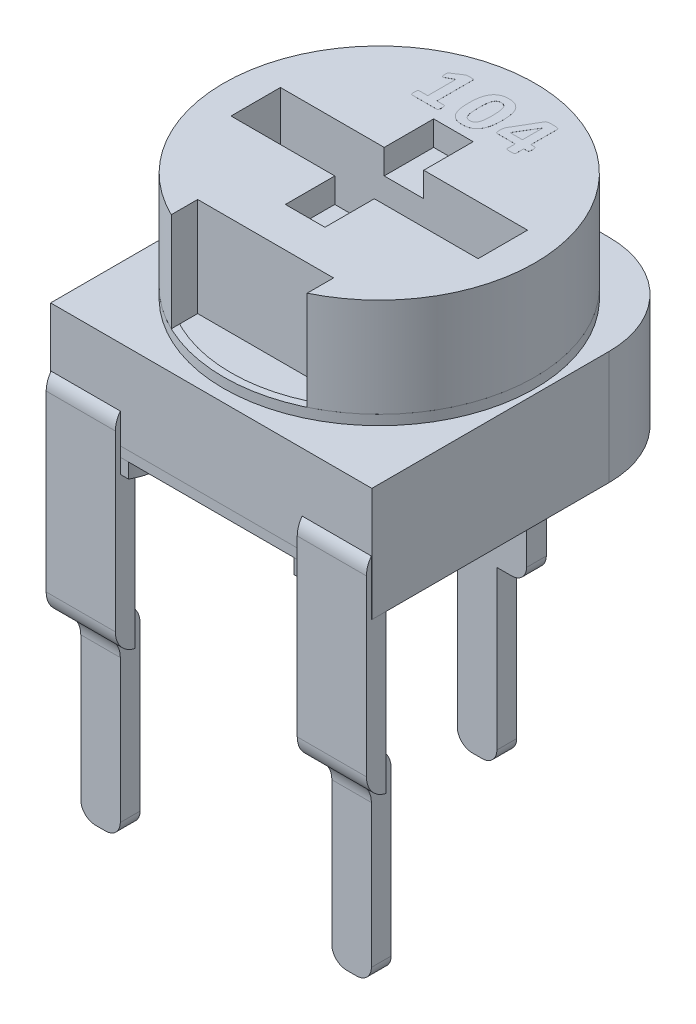
SolidWorks part; units mm, degrees
material "ABS"
ref_plane "Front Plane" through (0, 0, 0) normal (0, 0, 1) x (1, 0, 0)
ref_plane "Top Plane" through (0, 0, 0) normal (0, 1, 0) x (1, 0, 0)
ref_plane "Right Plane" through (0, 0, 0) normal (1, 0, 0) x (0, 0, -1)
sketch "Sketch1" plane through (0, 0, 0) normal (0, 1, 0) x (1, 0, 0)
  line L0 (0, 3.15) -> (0, -3.15) construction
  line L1 (0, 3.15) -> (0, 3.4) construction
  line L2 (0, -3.15) -> (0, -3.4) construction
  line L3 (-3.15, 0) -> (3.15, 0) construction
  line L4 (3.15, 0) -> (3.25, 0) construction
  line L5 (-3.15, 0) -> (-3.25, 0) construction
  line L6 (-3.25, -3.4) -> (3.25, -3.4)
  line L7 (-3.25, -3.4) -> (-3.25, 3.4)
  line L8 (-3.25, 3.4) -> (3.25, 3.4)
  line L9 (3.25, 3.4) -> (3.25, -3.4)
  circle A0 centre (0, 0) radius 3.15 construction
  dimension "D1" = 6.3
  dimension "D2" = 6.8
  dimension "D3" = 6.5
extrude "Boss-Extrude1" add sketch "Sketch1" along normal blind 2.3
sketch "Sketch2" plane through (0, 2.3, 0) normal (0, 1, 0) x (1, 0, 0)
  circle A0 centre (0, 0) radius 3.15 construction
  circle A1 centre (0, 0) radius 3.15
extrude "Boss-Extrude2" add sketch "Sketch2" along normal blind 0.2
fillet "Fillet1" radius 2 2 edges at (3.25, 1.15, -3.4) (-3.25, 1.15, -3.4)
sketch "Sketch3" plane through (0, 0, 0) normal (0, -1, 0) x (1, 0, 0)
  line L0 (0, 0) -> (0, -2.5) construction
  line L1 (-1.75, -2.5) -> (1.75, -2.5)
  line L6 (-2.25, -2) -> (-2.25, 2)
  line L7 (2.25, -2) -> (2.25, 2)
  line L8 (-2.25, 2) -> (-3, 2)
  line L9 (-3, 2) -> (-3, 3.4)
  line L10 (-3.25, 3.4) -> (3.25, 3.4) construction
  line L11 (2.25, 2) -> (3, 2)
  line L12 (3, 2) -> (3, 3.4)
  line L13 (3, 3.4) -> (-3, 3.4)
  line L14 (0, 0) -> (0, 3.4) construction
  arc A0 (-1.75, -2.5) -> (-2.25, -2) centre (-1.75, -2) cw
  arc A1 (1.75, -2.5) -> (2.25, -2) centre (1.75, -2) ccw
  point P20 (2.25, -2.5)
  dimension "D6" = 0.5
  dimension "D1" = 4.5
  dimension "D2" = 2.5
  dimension "D3" = 4.5
  dimension "D4" = 1.4
  dimension "D5" = 6
extrude "Cut-Extrude1" cut sketch "Sketch3" against normal blind 0.5
sketch "Sketch4" plane through (0, 0.5, 0) normal (0, -1, 0) x (1, 0, 0)
  line L8 (-3, 2) -> (-2.25, 2)
  line L9 (-2.25, 2) -> (-2.25, -2)
  line L10 (-1.75, -2.5) -> (1.75, -2.5)
  line L11 (2.25, -2) -> (2.25, 2)
  line L12 (2.25, 2) -> (3, 2)
  line L13 (3, 2) -> (3, 3.4)
  line L14 (3, 3.4) -> (-3, 3.4)
  line L15 (-3, 3.4) -> (-3, 2)
  line L16 (-3, 2) -> (-2.25, 2)
  line L17 (-2.25, 2) -> (-2.25, -2)
  line L18 (-1.75, -2.5) -> (1.75, -2.5)
  line L19 (2.25, -2) -> (2.25, 2)
  line L20 (2.25, 2) -> (3, 2)
  line L21 (3, 2) -> (3, 3.4)
  line L22 (3, 3.4) -> (-3, 3.4)
  line L23 (-3, 3.4) -> (-3, 2)
  arc A2 (-2.25, -2) -> (-1.75, -2.5) centre (-1.75, -2) ccw
  arc A3 (1.75, -2.5) -> (2.25, -2) centre (1.75, -2) ccw
  arc A4 (-2.25, -2) -> (-1.75, -2.5) centre (-1.75, -2) ccw
  arc A5 (1.75, -2.5) -> (2.25, -2) centre (1.75, -2) ccw
  dimension "D1" = 0
extrude "Boss-Extrude3" add sketch "Sketch4" along normal blind 0.2 separate body
sketch "Sketch5" plane through (0, 0.3, 0) normal (0, -1, 0) x (1, 0, 0)
  line L0 (0, 3.4) -> (0, 2.9) construction
  line L1 (3, 3.4) -> (-3, 3.4) construction
  line L2 (0, 2.9) -> (0, -2.18) construction
  line L3 (-2.54, 2.9) -> (2.54, 2.9) construction
  circle A0 centre (2.54, 2.9) radius 1
  circle A1 centre (-2.54, 2.9) radius 1
  circle A2 centre (0, -2.18) radius 1
  dimension "D2" = 5.08
  dimension "D4" = 2
  dimension "D1" = 0.5
  dimension "D3" = 5.08
extrude "Boss-Extrude4" add sketch "Sketch5" along normal up to surface (0.3 mm away) up to face at (0, 0, 0.1228)
sketch "Sketch6" plane through (0, 0.3, 0) normal (0, 1, 0) x (1, 0, 0)
  line L0 (-3.25, -3.4) -> (-3.25, -1)
  line L1 (-3.25, 1.4) -> (-3.25, -3.4) construction
  line L2 (-3.25, -1) -> (-4.35, -1)
  line L3 (-4.35, -1) -> (-4.35, -4.5)
  line L4 (-4.35, -4.5) -> (4.35, -4.5)
  line L5 (4.35, -4.5) -> (4.35, -1)
  line L6 (4.35, -1) -> (3.25, -1)
  line L7 (3.25, -3.4) -> (3.25, 1.4) construction
  line L8 (-3.25, -3.4) -> (3.25, -3.4)
  line L9 (3.25, -3.4) -> (3.25, -1)
  line L10 (0, 0) -> (0, -3.4) construction
  line L11 (0, -3.4) -> (0, -4.5) construction
  dimension "D1" = 3.5
extrude "Cut-Extrude2" cut sketch "Sketch6" against normal up to surface (0.3 mm away) up to face at (0, 0, -0.817)
sketch "Sketch8" plane through (0, 0.3, 0) normal (0, -1, 0) x (1, 0, 0)
  line L1 (-0.4, -1.98) -> (0.4, -1.98)
  line L2 (-0.4, -1.98) -> (-0.4, -2.38)
  line L3 (-0.4, -2.38) -> (0.4, -2.38)
  line L4 (0.4, -1.98) -> (0.4, -2.38)
  line L5 (-0.4, -1.98) -> (0.4, -2.38) construction
  line L6 (-0.4, -2.38) -> (0.4, -1.98) construction
  line L7 (-2.94, 3.1) -> (-2.14, 3.1)
  line L8 (-2.94, 3.1) -> (-2.94, 2.7)
  line L9 (-2.94, 2.7) -> (-2.14, 2.7)
  line L10 (-2.14, 3.1) -> (-2.14, 2.7)
  line L11 (-2.94, 3.1) -> (-2.14, 2.7) construction
  line L12 (-2.94, 2.7) -> (-2.14, 3.1) construction
  line L13 (2.94, 3.1) -> (2.14, 3.1)
  line L14 (2.94, 3.1) -> (2.94, 2.7)
  line L15 (2.94, 2.7) -> (2.14, 2.7)
  line L16 (2.14, 3.1) -> (2.14, 2.7)
  line L17 (2.94, 3.1) -> (2.14, 2.7) construction
  line L18 (2.94, 2.7) -> (2.14, 3.1) construction
  point P0 (0, -2.18)
  point P5 (-2.54, 2.9)
  point P11 (2.54, 2.9)
  dimension "D1" = 0.4
  dimension "D2" = 0.8
extrude "Boss-Extrude5" add sketch "Sketch8" along normal blind 7
sketch "Sketch9" plane through (0, 0.3, 0) normal (0, -1, 0) x (1, 0, 0)
  line L4 (0, -1.98) -> (0, -2.38) construction
  line L5 (0.4, -1.98) -> (-0.4, -1.98) construction
  line L6 (-0.4, -2.38) -> (0.4, -2.38) construction
  line L8 (-1, -1.98) -> (1, -1.98)
  line L9 (-1, -1.98) -> (-1, -2.38)
  line L10 (-1, -2.38) -> (1, -2.38)
  line L11 (1, -1.98) -> (1, -2.38)
  line L12 (-1, -1.98) -> (1, -2.38) construction
  line L13 (-1, -2.38) -> (1, -1.98) construction
  point P14 (0, -2.18)
  dimension "D1" = 2
extrude "Boss-Extrude6" add sketch "Sketch9" along normal blind 3.5
sketch "Sketch10" plane through (0, 0.3, 0) normal (0, -1, 0) x (1, 0, 0)
  line L0 (-2.54, 3.1) -> (-2.54, 3.5) construction
  line L1 (-2.14, 3.1) -> (-2.94, 3.1) construction
  line L2 (2.54, 3.1) -> (2.54, 3.5) construction
  line L3 (2.94, 3.1) -> (2.14, 3.1) construction
  line L4 (-2.94, 3.1) -> (-2.94, 2.7) construction
  line L5 (-3.24, 3.5) -> (-1.84, 3.5)
  line L6 (-3.24, 3.5) -> (-3.24, 3.1)
  line L7 (-3.24, 3.1) -> (-1.84, 3.1)
  line L8 (-1.84, 3.5) -> (-1.84, 3.1)
  line L10 (1.84, 3.5) -> (3.24, 3.5)
  line L11 (1.84, 3.5) -> (1.84, 3.1)
  line L12 (1.84, 3.1) -> (3.24, 3.1)
  line L13 (3.24, 3.5) -> (3.24, 3.1)
  dimension "D1" = 1.4
extrude "Boss-Extrude7" add sketch "Sketch10" along normal blind 3.5 and the other way blind 1
fillet "Fillet2" radius 0.5 2 edges at (2.54, 1.3, 3.5) (-2.54, 1.3, 3.5)
sketch "Sketch11" plane through (0, 0, 0) normal (1, 0, 0) x (0, 0, -1)
  line L0 (-3.4, 0) -> (1.4, 0) construction
  line L1 (-3.1, -2.8) -> (-2.7, -2.8)
  line L2 (-3.1, -2.8) -> (-3.1, 0)
  line L3 (-3.1, 0) -> (-2.7, 0)
  line L4 (-2.7, -2.8) -> (-2.7, 0)
  line L5 (-2.7, -6.7) -> (-2.7, 0.3) construction
  line L6 (-3.1, -2.8) -> (-3.1, -3.2) construction
extrude "Cut-Extrude3" cut sketch "Sketch11" against normal through all both and the other way through all
fillet "Fillet3" radius 0.5 4 edges at (-2.54, -2.8, 3.1) (2.54, -2.8, 3.1) (-2.54, -3.2, 3.5) (2.54, -3.2, 3.5)
fillet "Fillet4" radius 0.5 4 edges at (2.54, -2.8, 2.7) (-2.54, -2.8, 2.7) (2.54, -3.2, 3.1) (-2.54, -3.2, 3.1)
fillet "Fillet5" radius 0.3 12 edges at (-1, -3.2, -2.18) (1, -3.2, -2.18) (-0.4, -6.7, -2.18) (0.4, -6.7, -2.18) (2.14, -6.7, 2.9) (2.94, -6.7, 2.9) (-2.94, -6.7, 2.9) (-2.14, -6.7, 2.9) (-2.14, -2.7551, 3.1) (-2.94, -2.7551, 3.1) (2.14, -2.7551, 3.1) (2.94, -2.7551, 3.1)
sketch "Sketch12" plane through (0, 0.3, 0) normal (0, -1, 0) x (1, 0, 0)
  circle A0 centre (0, 0) radius 2
  circle A1 centre (0, 0) radius 1.5
  dimension "D1" = 4
  dimension "D2" = 3
extrude "Boss-Extrude8" add sketch "Sketch12" along normal blind 0.15
sketch "Sketch15" plane through (0, 2.5, 0) normal (0, 1, 0) x (1, 0, 0)
  circle A0 centre (0, 0) radius 3
  dimension "D1" = 6
extrude "Cut-Extrude4" cut sketch "Sketch15" against normal blind 0.5
sketch "Sketch14" plane through (0, 2.5, 0) normal (0, 1, 0) x (1, 0, 0)
  circle A1 centre (0, 0) radius 3.15
  circle A2 centre (0, 0) radius 3.15
  dimension "D1" = 0
extrude "Boss-Extrude9" add sketch "Sketch14" along normal blind 2 separate body
sketch "Set Angle of Knob" plane through (0, 4.5, 0) normal (0, 1, 0) x (1, 0, 0)
  line L0 (0, 0) -> (0, -3.15) construction
  line L1 (-2.5, 0) -> (2.5, 0) construction
  line L2 (-2.5, 0.5) -> (-2.5, -0.5)
  line L3 (2.5, 0.5) -> (2.5, -0.5)
  line L4 (-2.5, 0.5) -> (-0.4, 0.5)
  line L5 (-2.5, -0.5) -> (-0.4, -0.5)
  line L6 (0, 0) -> (0, -1.5) construction
  line L7 (0, 0) -> (0, 1.5) construction
  line L8 (0, 1.5) -> (0, 3.15) construction
  line L9 (0.4, 1.5) -> (-0.4, 1.5)
  line L10 (0.4, 1.5) -> (0.4, 0.5)
  line L11 (-0.4, 1.5) -> (-0.4, 0.5)
  line L12 (0.4, 0.5) -> (2.5, 0.5)
  line L13 (-0.4, -1.5) -> (0.4, -1.5)
  line L14 (-0.4, -1.5) -> (-0.4, -0.5)
  line L15 (0.4, -1.5) -> (0.4, -0.5)
  line L16 (0.4, -0.5) -> (2.5, -0.5)
  line L17 (0, -1.5) -> (0, -2.3) construction
  line L18 (-1.375, -2.3) -> (1.375, -2.3)
  line L19 (-1.375, -2.3) -> (-1.375, -3.8)
  line L20 (1.375, -2.3) -> (1.375, -3.8)
  line L21 (-1.375, -3.8) -> (1.375, -3.8)
  line L22 (-1, 0.25) -> (1, 0.25) construction
  line L23 (-1, 0.25) -> (-1, -0.25) construction
  line L24 (-1, -0.25) -> (1, -0.25) construction
  line L25 (1, -0.25) -> (1, 0.25) construction
  circle A0 centre (0, 0) radius 3.15 construction
  circle A1 centre (0, 0) radius 3.15 construction
  point P32 (0, 0.25)
  dimension "D1" = 1
  dimension "D2" = 0.8
  dimension "D3" = 1.5
  dimension "D4" = 5
  dimension "D5" = 90
  dimension "D6" = 2.75
  dimension "D7" = 1.5
  dimension "D8" = 1.8
  dimension "D9" = 0.25
  dimension "D10" = 0.25
  dimension "D11" = 2
extrude "TURN KNOB" cut sketch "Set Angle of Knob" against normal blind 2.3
sketch "Sketch17" plane through (0, 2, 0) normal (0, 1, 0) x (1, 0, 0)
  line L0 (-0.4, -1.5) -> (0.4, -1.5)
  line L1 (0.4, -1.5) -> (0.4, -0.5)
  line L2 (0.4, 1.5) -> (-0.4, 1.5)
  line L3 (-0.4, 1.5) -> (-0.4, 0.5)
  line L4 (-0.4, 0.5) -> (0.4, 0.5)
  line L5 (-0.4, -0.5) -> (0.4, -0.5)
  line L6 (-0.4, -0.5) -> (-0.4, -1.5)
  line L7 (0.4, 0.5) -> (0.4, 1.5)
extrude "Boss-Extrude10" add sketch "Sketch17" along normal blind 2
sketch "Sketch20" plane through (0, 2, 0) normal (0, 1, 0) x (1, 0, 0)
  line L0 (-1, 0.25) -> (1, 0.25) construction
  line L1 (-1, 0.25) -> (1, 0.25)
  line L2 (-1, -0.25) -> (1, -0.25) construction
  line L3 (-1, -0.25) -> (1, -0.25)
  line L4 (-1, 0.25) -> (-1, -0.25) construction
  line L5 (-1, 0.25) -> (-1, -0.25)
  line L6 (1, -0.25) -> (1, 0.25) construction
  line L7 (1, -0.25) -> (1, 0.25)
extrude "Cut-Extrude6" cut sketch "Sketch20" against normal blind 0.5
fillet "Fillet6" radius 0.2 2 edges at (1, 2, 0) (-1, 2, 0)
sketch "See Code in Properties" plane through (0, 4.5, 0) normal (0, 1, 0) x (1, 0, 0)
  line L0 (0, 1.5) -> (0, 1.7) construction
  line L1 (0.4, 1.5) -> (-0.4, 1.5) construction
  line L2 (0, 1.5) -> (0, 3.15) construction
  line L3 (-1.5, 1.7) -> (1.5, 1.7) construction
  text T0 "104" font "Calibri" height 0.9
  dimension "D1" = 0.2
  dimension "D2" = 3
extrude "Code Number" add sketch "See Code in Properties" along normal blind 0.001
